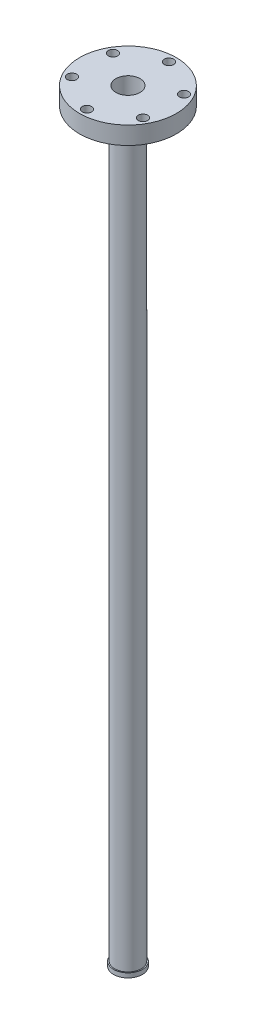
SolidWorks part; units mm, degrees
ref_plane "Front Plane" through (0, 0, 0) normal (0, 0, 1) x (1, 0, 0)
ref_plane "Top Plane" through (0, 0, 0) normal (0, 1, 0) x (1, 0, 0)
ref_plane "Right Plane" through (0, 0, 0) normal (1, 0, 0) x (0, 0, -1)
sketch "Sketch1" plane through (0, 0, 0) normal (0, 1, 0) x (1, 0, 0)
  circle A0 centre (0, 0) radius 9.525
  circle A1 centre (0, 0) radius 8.636
  dimension "D1" = 19.05
  dimension "D2" = 17.272
extrude "Extrude1" add sketch "Sketch1" along normal blind 546.1
sketch "Sketch2" plane through (0, 546.1, 0) normal (0, 1, 0) x (1, 0, 0)
  circle A0 centre (0, 0) radius 8.636
  circle A1 centre (0, 0) radius 34.671
  dimension "D1" = 69.342
extrude "Extrude2" add sketch "Sketch2" against normal blind 12.7
sketch "Sketch3" plane through (0, 546.1, 0) normal (0, 1, 0) x (1, 0, 0)
  line L0 (0, 0) -> (0, 29.3624) construction
  circle A0 centre (0, 29.3624) radius 3.3655
  dimension "D1" = 6.731
  dimension "D2" = 29.3624
extrude "Extrude3" cut sketch "Sketch3" against normal through all
pattern_circular "CirPattern1" count 6 over 360 about axis through (0, 546.1, 0) along (0, -1, 0) of "Extrude3"
sketch "Sketch4" plane through (0, 0, 0) normal (0, -1, 0) x (1, 0, 0)
  circle A0 centre (0, 0) radius 8.636
  circle A1 centre (0, 0) radius 10.3187
  dimension "D1" = 20.6375
extrude "Extrude4" add sketch "Sketch4" against normal blind 3.175
